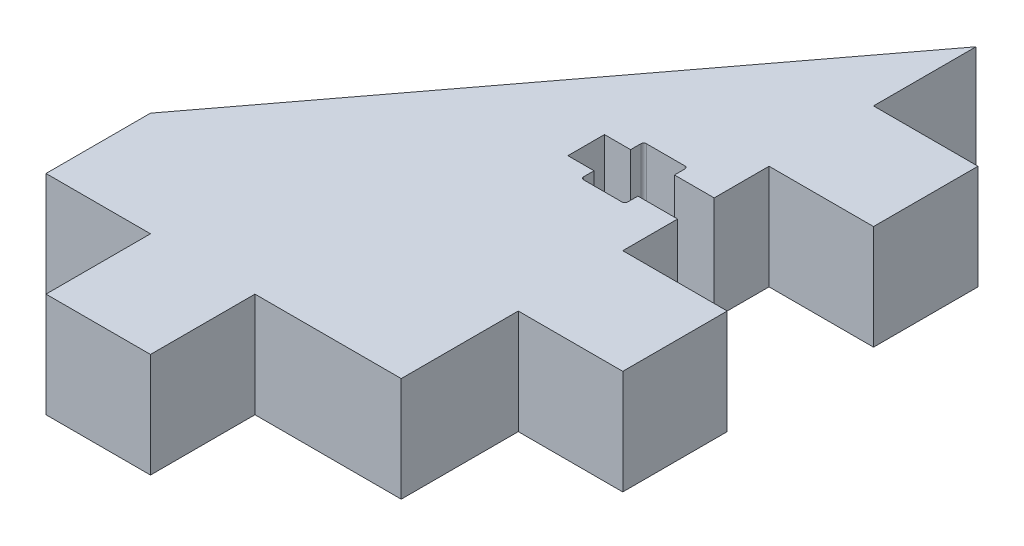
SolidWorks part; units mm, degrees
ref_plane "Front Plane" through (0, 0, 0) normal (0, 0, 1) x (1, 0, 0)
ref_plane "Top Plane" through (0, 0, 0) normal (0, 1, 0) x (1, 0, 0)
ref_plane "Right Plane" through (0, 0, 0) normal (1, 0, 0) x (0, 0, -1)
sketch "Sketch1" plane through (0, 0, 0) normal (0, 1, 0) x (1, 0, 0)
  line L0 (0, 0) -> (-14, 0)
  line L1 (-14, 0) -> (-14, -10)
  line L2 (-14, -10) -> (-24, -10)
  line L3 (-24, -10) -> (-24, 0)
  line L4 (-24, 0) -> (-34, 0)
  line L5 (-34, 0) -> (-34, 10)
  line L6 (-34, 10) -> (0, 55)
  line L7 (0, 55) -> (0, 45.2)
  line L8 (0, 45.2) -> (10, 45.2)
  line L9 (10, 45.2) -> (10, 35.2)
  line L10 (10, 35.2) -> (0, 35.2)
  line L11 (0, 35.2) -> (0, 21.2)
  line L12 (-24, 0) -> (-14, 0) construction
  line L13 (-19, 0) -> (-19, -10) construction
  line L14 (0, 16.2) -> (0, 11.2) construction
  line L15 (5, 11.2) -> (5, 21.2) construction
  line L24 (0, 21.2) -> (10, 21.2)
  line L25 (10, 21.2) -> (10, 11.2)
  line L26 (10, 11.2) -> (0, 11.2)
  line L27 (0, 11.2) -> (0, 0)
  line L32 (10, 40.2) -> (0, 40.2) construction
  line L33 (0, 40.2) -> (0, 35.2) construction
  line L34 (10, 16.2) -> (0, 16.2) construction
  line L35 (0, 16.2) -> (0, 21.2) construction
  dimension "D2" = 10
  dimension "D3" = 10
  dimension "D7" = 10
  dimension "D8" = 10
  dimension "D10" = 10
  dimension "D11" = 10
  dimension "D12" = 10
  dimension "D9" = 55
  dimension "D5" = 16.2
  dimension "D13" = 24
  dimension "D4" = 24
  dimension "D6" = 24
extrude "Boss-Extrude1" add sketch "Sketch1" along normal blind 10
sketch "Sketch2" [suppressed] plane through (0, 8, 0) normal (0, 1, 0) x (1, 0, 0)
  line L0 (0, 29.9) -> (0, 25.9) construction
  line L1 (0, 27.9) -> (-7.2, 27.9) construction
  line L2 (-7.2, 25.9) -> (-7.2, 29.9) construction
  line L3 (7.5, 36.4) -> (7.5, 20.4) construction
  line L4 (0, 36.4) -> (7.5, 36.4) construction
  line L5 (0, 27.9) -> (7.5, 27.9) construction
sketch "Sketch3" plane through (0, 10, 0) normal (0, 1, 0) x (1, 0, 0)
  line L0 (0, 28.2) -> (-10.5, 28.2) construction
  line L1 (0, 21.2) -> (0, 35.2) construction
  line L2 (-10.5, 29.95) -> (-8, 29.95)
  line L3 (-8, 29.95) -> (-8, 30.95)
  line L4 (-7.75, 31.2) -> (-4.05, 31.2)
  line L5 (-3.8, 30.95) -> (-3.8, 29.95)
  line L6 (-3.8, 29.95) -> (0, 29.95)
  line L7 (0, 29.95) -> (0, 26.45)
  line L8 (-10.5, 29.95) -> (-10.5, 26.45)
  line L9 (-3.8, 26.45) -> (0, 26.45)
  line L10 (-3.8, 25.45) -> (-3.8, 26.45)
  line L11 (-7.75, 25.2) -> (-4.05, 25.2)
  line L12 (-8, 26.45) -> (-8, 25.45)
  line L13 (-10.5, 26.45) -> (-8, 26.45)
  arc A0 (-8, 30.95) -> (-7.75, 31.2) centre (-7.75, 30.95) cw
  arc A1 (-4.05, 31.2) -> (-3.8, 30.95) centre (-4.05, 30.95) cw
  arc A2 (-4.05, 25.2) -> (-3.8, 25.45) centre (-4.05, 25.45) ccw
  arc A3 (-8, 25.45) -> (-7.75, 25.2) centre (-7.75, 25.45) ccw
  point P12 (-8, 31.2)
  point P15 (-3.8, 31.2)
  point P26 (-3.8, 25.2)
  point P27 (-8, 25.2)
  dimension "D7" = 0.25
  dimension "D1" = 10.5
  dimension "D3" = 1.75
  dimension "D2" = 8
  dimension "D4" = 4.2
  dimension "D5" = 3
  dimension "D6" = 1.75
extrude "Cut-Extrude1" cut sketch "Sketch3" against normal through all
equation "\"Y-ROD-SPACING\"=75"
equation "\"Y-BED-OFFSET\"=2"
equation "\"Y-BED-ROD-INSET\"=3.5"
equation "\"T-SLOT-NUT-FILLET-RADIUS\"=0.25"
equation "\"T-SLOT-SCREW-SHAFT-RADIUS\"=1.75"
equation "\"T-SLOT-SCREW-SHAFT-CUTOUT-LENGTH\"=10.5"
equation "\"T-SLOT-NUT-DEPTH\"=4.2"
equation "\"T-SLOT-NUT-WIDTH\"=3"
equation "\"T-SLOT-NUT-END-DISTANCE\"=8"
equation "\"ACRYLIC-TAB-CUTOUT-SIZE\"=\"ACRYLIC-THICKNESS\"+\"ACRYLIC-TAB-TOLERANCE\"*2"
equation "\"ACRYLIC-TAB-WIDTH\"=\"ACRYLIC-THICKNESS\""
equation "\"ACRYLIC-M3-HOLE\"=3.2"
equation "\"SMOOTHROD-CAP-SCREW-DISTANCE\"=20"
equation "\"FRAME-WIDTH-INNER\"=370"
equation "\"NEMA17-HOLE-SPACING\"=31"
equation "\"NEMA17-CENTRAL-CUTOUT\"=22.5"
equation "\"D3@Sketch1\"=\"ACRYLIC-TAB-WIDTH\""
equation "\"D12@Sketch1\"=\"ACRYLIC-TAB-WIDTH\""
equation "\"D2@Sketch1\"=\"ACRYLIC-TAB-WIDTH\""
equation "\"D11@Sketch1\"=\"ACRYLIC-TAB-WIDTH\""
equation "\"D1@Sketch1\"=\"ACRYLIC-TAB-WIDTH\""
equation "\"D10@Sketch1\"=\"ACRYLIC-TAB-WIDTH\""
equation "\"Z-BRACKET-REACH\"=55"
equation "\"D9@Sketch1\"=\"Z-BRACKET-REACH\""
equation "\"D6@Sketch3\"=\"T-SLOT-SCREW-SHAFT-RADIUS\""
equation "\"D3@Sketch3\"=\"T-SLOT-SCREW-SHAFT-RADIUS\""
equation "\"D4@Sketch3\"=\"T-SLOT-NUT-DEPTH\""
equation "\"D7@Sketch3\"=\"T-SLOT-NUT-FILLET-RADIUS\""
equation "\"D1@Sketch3\"=\"T-SLOT-SCREW-SHAFT-CUTOUT-LENGTH\""
equation "\"D5@Sketch3\"=\"T-SLOT-NUT-WIDTH\""
equation "\"D2@Sketch3\"=\"T-SLOT-NUT-END-DISTANCE\""
equation "\"X-ROD-SPACING\"=45"
equation "\"Z-ROD-SPACING\"=17.5"
equation "\"ACRYLIC-THICKNESS\"=10"
equation "\"ACRYLIC-THICKNESS2\"=4.5"
equation "\"TOP-BRACKET-SPACING\"=40"
equation "\"SMOOTHROD-X-LENGTH\"=350"
equation "\"SMOOTHROD-Y-LENGTH\"=350"
equation "\"SMOOTHROD-Z-LENGTH\"=350"
equation "\"SMOOTHROD-TIGHTENING-HEADROOM\"=1"
equation "\"LEADSCREW-Z-LENGTH\"=300"
equation "\"SCREW-LENGTH-FRAME\"=\"ACRYLIC-THICKNESS\" + 10"
equation "\"SCREW-HEAD-RADIUS\"=6"
equation "\"PRINTED-X-SMOOTHROD-DIAMETER\"=8.2"
equation "\"PRINTED-X-SMOOTHROD-CUTOUT\"=10"
equation "\"PRINTED-X-BASE-HEIGHT\"=10"
equation "\"PRINTED-LM8UU-CUTOUT-SIZE\"=15.25"
equation "\"PRINTED-LM8UU-CUTOUT-LENGTH\"=24.5"
equation "\"PRINTED-X-IDLER-HEIGHT\"=16"
equation "\"PSU-MOUNTING-WIDTH\"=95"
equation "\"PSU-MOUNTING-HEIGHT\"=177"
equation "\"D1@Boss-Extrude1\"=\"ACRYLIC-THICKNESS\""
